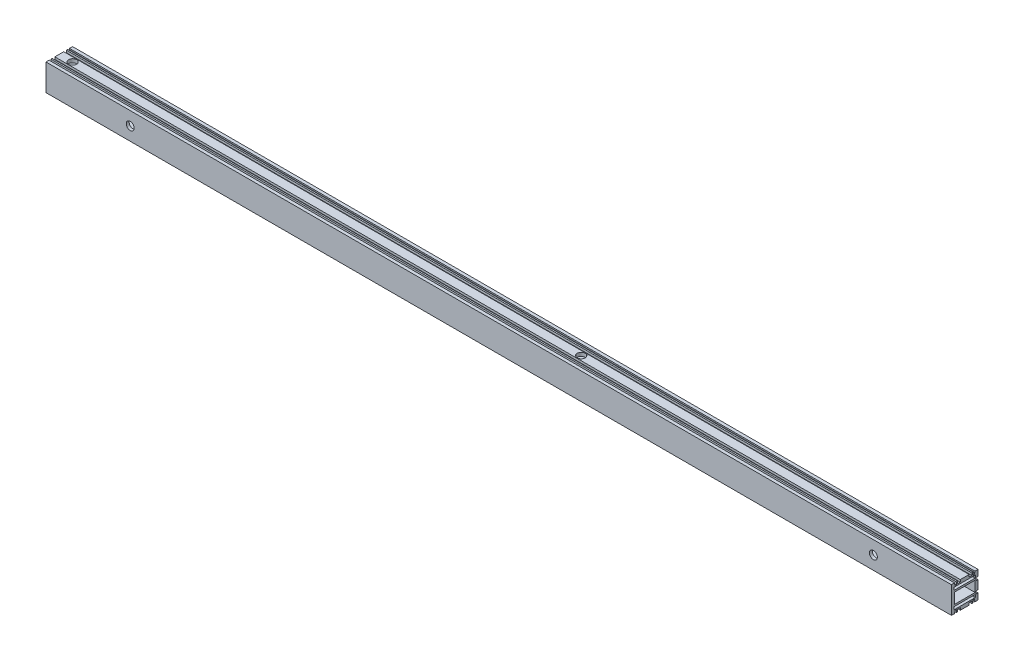
SolidWorks part; units mm, degrees
ref_plane "前视基准面" through (0, 0, 0) normal (0, 0, 1) x (1, 0, 0)
ref_plane "上视基准面" through (0, 0, 0) normal (0, 1, 0) x (1, 0, 0)
ref_plane "右视基准面" through (0, 0, 0) normal (1, 0, 0) x (0, 0, -1)
sketch "草图1" plane through (0, 0, 0) normal (1, 0, 0) x (0, 0, -1)
  line L0 (-15, 15) -> (15, -15) construction
  line L1 (-15, 15) -> (-11.5, 15)
  line L2 (-15, 15) -> (-15, -15)
  line L3 (-15, -15) -> (-11.5, -15)
  line L4 (15, 15) -> (15, 8)
  line L5 (15, 15) -> (-15, -15) construction
  line L6 (-11.5, 15) -> (-11.5, 13.5)
  line L7 (-11.5, 13.5) -> (-11, 13.5)
  line L8 (-11, 13.5) -> (-11, 12)
  line L9 (-11, 12) -> (-9.5, 12)
  line L10 (-9.5, 12) -> (-9.5, 15)
  line L11 (-9.5, 15) -> (-8, 15)
  line L12 (-8, 15) -> (-8, 12.5)
  line L13 (-8, 12.5) -> (-5, 12.5)
  line L14 (-5, 12.5) -> (-5, 15)
  line L15 (-5, 15) -> (5, 15)
  line L16 (0, 21.5201) -> (0, -18.309) construction
  line L17 (0, 55) -> (0, -55) construction
  line L18 (5, 12.5) -> (5, 15)
  line L19 (8, 12.5) -> (5, 12.5)
  line L20 (8, 15) -> (8, 12.5)
  line L21 (9.5, 15) -> (8, 15)
  line L22 (9.5, 12) -> (9.5, 15)
  line L23 (11, 12) -> (9.5, 12)
  line L24 (11, 13.5) -> (11, 12)
  line L25 (11.5, 13.5) -> (11, 13.5)
  line L26 (11.5, 15) -> (11.5, 13.5)
  line L27 (8, 15) -> (9.5, 15)
  line L28 (11.5, 15) -> (15, 15)
  line L29 (-19.8303, 0) -> (22.13, 0) construction
  line L30 (55, 0) -> (-55, 0) construction
  line L31 (8, -15) -> (9.5, -15)
  line L32 (11.5, -15) -> (11.5, -13.5)
  line L33 (11.5, -13.5) -> (11, -13.5)
  line L34 (11, -13.5) -> (11, -12)
  line L35 (11, -12) -> (9.5, -12)
  line L36 (9.5, -12) -> (9.5, -15)
  line L37 (9.5, -15) -> (8, -15)
  line L38 (8, -15) -> (8, -12.5)
  line L39 (8, -12.5) -> (5, -12.5)
  line L40 (5, -12.5) -> (5, -15)
  line L41 (-5, -15) -> (5, -15)
  line L42 (-5, -12.5) -> (-5, -15)
  line L43 (-8, -12.5) -> (-5, -12.5)
  line L44 (-8, -15) -> (-8, -12.5)
  line L45 (-9.5, -15) -> (-8, -15)
  line L46 (-9.5, -12) -> (-9.5, -15)
  line L47 (-11, -12) -> (-9.5, -12)
  line L48 (-11, -13.5) -> (-11, -12)
  line L49 (-11.5, -13.5) -> (-11, -13.5)
  line L50 (-11.5, -15) -> (-11.5, -13.5)
  line L51 (-9.5, -15) -> (-8, -15)
  line L52 (-5, -15) -> (5, -15)
  line L53 (8, -15) -> (9.5, -15)
  line L54 (11.5, -15) -> (15, -15)
  line L55 (15, 8) -> (12.5, 8)
  line L56 (12.5, 8) -> (12.5, 5)
  line L57 (12.5, 5) -> (15, 5)
  line L58 (12.5, -5) -> (15, -5)
  line L59 (12.5, -8) -> (12.5, -5)
  line L60 (15, -8) -> (12.5, -8)
  line L61 (15, 5) -> (15, -5)
  line L62 (15, -8) -> (15, -15)
  line L63 (12, -10.5) -> (12, -8.5)
  line L64 (-11.5, 11) -> (11.5, 11)
  line L65 (-12, 10.5) -> (-12, 8.5)
  line L66 (-11.5, 8) -> (11.5, 8)
  line L67 (12, 10.5) -> (12, 8.5)
  line L68 (-11.5, -8) -> (11.5, -8)
  line L69 (-12, -10.5) -> (-12, -8.5)
  line L70 (-11.5, -11) -> (11.5, -11)
  line L72 (-11.75, 6) -> (11.75, 6)
  line L73 (-11.75, 6) -> (-11.75, -6)
  line L74 (-11.75, -6) -> (11.75, -6)
  line L75 (11.75, 6) -> (11.75, -6)
  arc A0 (12, 8.5) -> (11.5, 8) centre (11.5, 8.5) cw
  arc A1 (11.5, 11) -> (12, 10.5) centre (11.5, 10.5) cw
  arc A2 (-11.5, 11) -> (-12, 10.5) centre (-11.5, 10.5) ccw
  arc A3 (-11.5, 8) -> (-12, 8.5) centre (-11.5, 8.5) cw
  arc A8 (-11.5, -8) -> (-12, -8.5) centre (-11.5, -8.5) ccw
  arc A9 (-11.5, -11) -> (-12, -10.5) centre (-11.5, -10.5) cw
  arc A10 (11.5, -11) -> (12, -10.5) centre (11.5, -10.5) ccw
  arc A11 (12, -8.5) -> (11.5, -8) centre (11.5, -8.5) ccw
  point P69 (12, 11)
  point P72 (-12, 11)
  point P77 (-11, -13.5)
  point P80 (11, -13.5)
  point P83 (11, 13.5)
  point P86 (-11, 13.5)
  point P99 (-12, -11)
  point P100 (12, -11)
  dimension "D17" = 0.5
  dimension "D1" = 3.5
  dimension "D2" = 1.5
  dimension "D3" = 0.5
  dimension "D4" = 1.5
  dimension "D5" = 3
  dimension "D6" = 30
  dimension "D7" = 30
  dimension "D8" = 1.5
  dimension "D9" = 2.5
  dimension "D10" = 3
  dimension "D11" = 2.5
  dimension "D12" = 7
  dimension "D13" = 3
  dimension "D14" = 4
  dimension "D15" = 3
  dimension "D16" = 24
  dimension "D19" = 23.5
  dimension "D20" = 12
extrude "凸台-拉伸1" add sketch "草图1" along normal mid plane 1021 contours L2 L3 L50 L49 L48 L47 L46 L45 L44 L43 L42 L41 L40 L39 L38 L31 L36 L35 L34 L33 L32 L54 L62 L60 L59 L58 L61 L57 L56 L55 L4 L28 L26 L25 L24 L23 L22 L21 L20 L19 L18 L15 L14 L13 region at (0, 14.5757, 13.25)
hole_wizard "M6 螺纹孔1" positions "草图3" profile "草图2" tap size "M6" standard "GB"
sketch "草图3" plane through (0, -15, 0) normal (0, -1, 0) x (-1, 0, 0)
  line L0 (-510.5, -15) -> (510.5, -15) construction
  line L1 (510.5, -5) -> (510.5, 5) construction
  line L2 (-510.5, 15) -> (510.5, 15) construction
  point P0 (460.5, 0)
  point P3 (445.5, 0)
  point P6 (-133, 0)
  point P9 (-148, 0)
  point P12 (-218, 0)
  point P15 (-233, 0)
  point P18 (-445.5, 0)
  point P21 (-460.5, 0)
  point P24 (262.5, 0)
  point P26 (211.5, 0)
  point P33 (160.5, 0)
  dimension "D1" = 15
  dimension "D2" = 15
  dimension "D3" = 51
  dimension "D4" = 248
  dimension "D5" = 350
  dimension "D6" = 15
sketch "草图2" plane through (-460.5, -15, 0) normal (1, 0, 0) x (0, 0, -1)
  line L0 (0, 0) -> (0, 20.5022)
  line L1 (0, 20.5022) -> (2.5, 19)
  line L2 (2.5, 19) -> (2.5, 0)
  line L5 (2.5, 0) -> (0, 0)
  line L10 (0, 20.5022) -> (-2.5, 19) construction
  line L11 (0, -6.35) -> (0, 107.95) construction
  dimension "螺纹孔钻头直径" = 5
  dimension "螺纹孔钻头深度" = 19
  dimension "导头角度" = 118
cosmetic thread "孔螺蚊线1" parameters "D1"=9, "D2"=6
cosmetic thread "孔螺蚊线2" parameters "D1"=9, "D2"=6
cosmetic thread "孔螺蚊线3" parameters "D1"=9, "D2"=6
cosmetic thread "孔螺蚊线4" parameters "D1"=9, "D2"=6
cosmetic thread "孔螺蚊线5" parameters "D1"=9, "D2"=6
cosmetic thread "孔螺蚊线6" parameters "D1"=9, "D2"=6
cosmetic thread "孔螺蚊线7" parameters "D1"=9, "D2"=6
cosmetic thread "孔螺蚊线8" parameters "D1"=9, "D2"=6
cosmetic thread "孔螺蚊线15" parameters "D1"=9, "D2"=6
cosmetic thread "孔螺蚊线16" parameters "D1"=9, "D2"=6
cosmetic thread "孔螺蚊线18" parameters "D1"=9, "D2"=6
hole_wizard "M6 螺纹孔2" positions "草图5" profile "草图4" tap size "M6" standard "GB"
sketch "草图5" plane through (0, 0, -15) normal (0, 0, -1) x (-1, 0, 0)
  point P0 (460.5, 0)
  point P3 (445.5, 0)
  point P6 (157.5, 0)
  point P9 (142.5, 0)
  point P12 (-445.5, 0)
  point P15 (-460.5, 0)
sketch "草图4" plane through (-460.5, 0, -15) normal (1, 0, 0) x (0, 1, 0)
  line L0 (0, 0) -> (0, 20.5022)
  line L1 (0, 20.5022) -> (2.5, 19)
  line L2 (2.5, 19) -> (2.5, 0)
  line L5 (2.5, 0) -> (0, 0)
  line L10 (0, 20.5022) -> (-2.5, 19) construction
  line L11 (0, -6.35) -> (0, 107.95) construction
  dimension "螺纹孔钻头直径" = 5
  dimension "螺纹孔钻头深度" = 19
  dimension "导头角度" = 118
cosmetic thread "孔螺蚊线9" parameters "D1"=3.25, "D2"=6
cosmetic thread "孔螺蚊线10" parameters "D1"=3.25, "D2"=6
cosmetic thread "孔螺蚊线11" parameters "D1"=3.25, "D2"=6
cosmetic thread "孔螺蚊线12" parameters "D1"=3.25, "D2"=6
cosmetic thread "孔螺蚊线13" parameters "D1"=3.25, "D2"=6
cosmetic thread "孔螺蚊线14" parameters "D1"=3.25, "D2"=6
sketch "草图6" plane through (0, 15, 0) normal (0, 1, 0) x (1, 0, 0)
  line L0 (510.5, 15) -> (-510.5, 15) construction
  line L1 (510.5, 15) -> (-510.5, 15) construction
  line L2 (-510.5, -5) -> (-510.5, 5) construction
  line L3 (510.5, -5) -> (510.5, 5) construction
  circle A0 centre (-495.5, 0) radius 4.5
  circle A1 centre (78, 0) radius 4.5
  dimension "D4" = 9
  dimension "D6" = 9
  dimension "D1" = 15
  dimension "D2" = 15
  dimension "D3" = 15
  dimension "D5" = 432.5
extrude "切除-拉伸1" cut sketch "草图6" against normal through all
sketch "草图7" plane through (0, 0, 15) normal (0, 0, 1) x (1, 0, 0)
  line L0 (510.5, 15) -> (-510.5, 15) construction
  line L1 (-510.5, 15) -> (-510.5, -15) construction
  line L2 (510.5, 15) -> (510.5, -15) construction
  circle A0 centre (-415.5, 0) radius 4.5
  circle A1 centre (422.5, 0) radius 4.5
  dimension "D2" = 9
  dimension "D5" = 9
  dimension "D1" = 15
  dimension "D3" = 95
  dimension "D4" = 15
  dimension "D6" = 88
extrude "切除-拉伸2" cut sketch "草图7" against normal through all
hole_wizard "M4 螺纹孔1" positions "草图9" profile "草图8" tap size "M4" standard "GB"
sketch "草图9" plane through (0, 0, -15) normal (0, 0, -1) x (-1, 0, 0)
  line L0 (-510.5, -15) -> (510.5, -15) construction
  line L1 (510.5, 5) -> (510.5, -5) construction
  point P0 (343.5, 0)
  dimension "D1" = 15
  dimension "D2" = 167
sketch "草图8" plane through (-343.5, 0, -15) normal (1, 0, 0) x (0, 1, 0)
  line L0 (0, 0) -> (0, 12.4914)
  line L1 (0, 12.4914) -> (1.65, 11.5)
  line L2 (1.65, 11.5) -> (1.65, 0)
  line L5 (1.65, 0) -> (0, 0)
  line L10 (0, 12.4914) -> (-1.65, 11.5) construction
  line L11 (0, -6.35) -> (0, 107.95) construction
  dimension "螺纹孔钻头直径" = 3.3
  dimension "螺纹孔钻头深度" = 11.5
  dimension "导头角度" = 118
cosmetic thread "孔螺蚊线17" parameters "D1"=3.25, "D2"=4
